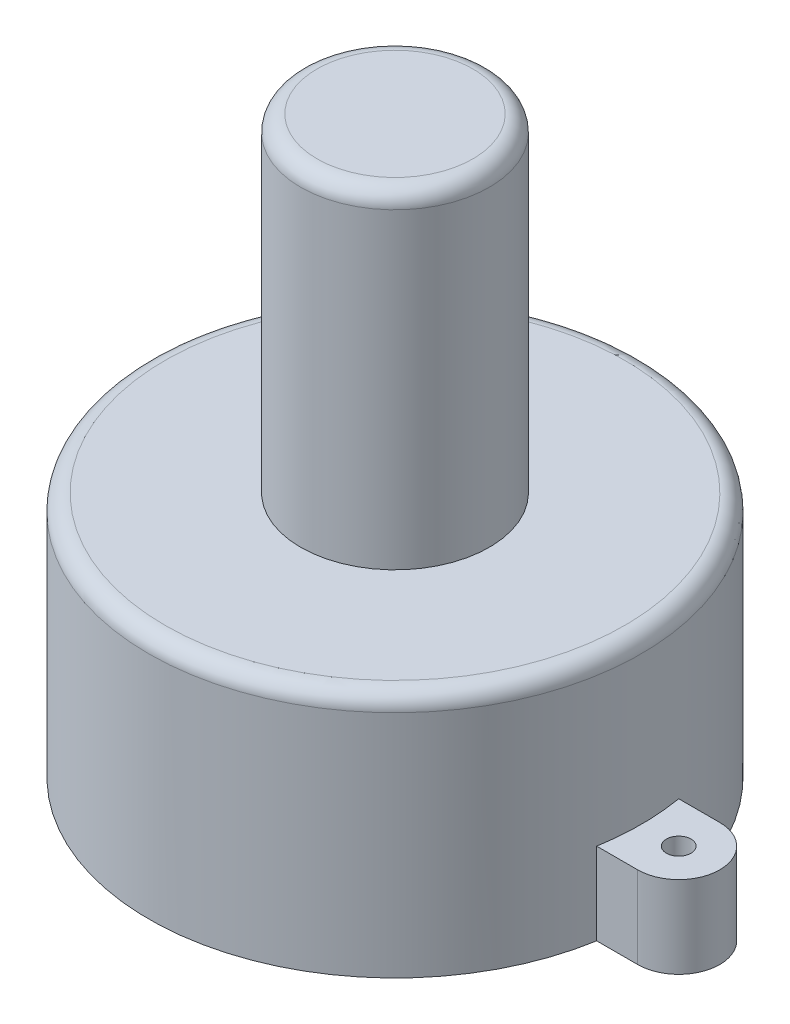
SolidWorks part; units mm, degrees
ref_plane "前基準面" through (0, 0, 0) normal (0, 0, 1) x (1, 0, 0)
ref_plane "上基準面" through (0, 0, 0) normal (0, 1, 0) x (1, 0, 0)
ref_plane "右基準面" through (0, 0, 0) normal (1, 0, 0) x (0, 0, -1)
sketch "草圖1" plane through (0, 0, 0) normal (0, 1, 0) x (1, 0, 0)
  circle A0 centre (0, 0) radius 30
  circle A1 centre (0, 0) radius 11.5
  dimension "D1" = 23
  dimension "D2" = 60
extrude "填料-伸長1" add sketch "草圖1" along normal blind 30 contours A0 A1 | A1 region at (-29.1515, 0, 0) region at (0, 0, 0)
extrude "填料-伸長2" add sketch "草圖1<3>" along normal blind 70 contours A1 region at (0, 0, 0)
sketch "草圖1<3>" plane through (0, 0, 0) normal (0, 1, 0) x (1, 0, 0) same geometry as "草圖1"
sketch "草圖3" plane through (0, 0, 0) normal (0, -1, 0) x (1, 0, 0)
  line L0 (0, 0) -> (0, 42.7) construction
  line L1 (0, 0) -> (52.9231, 0) construction
  line L2 (29.5804, 5) -> (39.5804, 5)
  line L3 (39.5804, 5) -> (39.5804, -5)
  line L4 (29.5804, -5) -> (39.5804, -5)
  line L5 (-29.5804, -5) -> (-39.5804, -5)
  line L6 (-39.5804, 5) -> (-39.5804, -5)
  line L7 (-29.5804, 5) -> (-39.5804, 5)
  circle A0 centre (0, 0) radius 30 construction
  arc A1 (29.5804, -5) -> (29.5804, 5) centre (0, 0) ccw
  arc A2 (-29.5804, -5) -> (-29.5804, 5) centre (0, 0) cw
  point P7 (39.5804, 0)
  dimension "D1" = 10
  dimension "D2" = 5
extrude "填料-伸長3" add sketch "草圖3" against normal blind 10
fillet "圓角1" 2 edges at (-39.5804, 5, 5) (-39.5804, 5, -5) type full round first side face at (-34.5804, 5, 5) second side face at (-34.5804, 5, -5) middle face at (-39.5804, 5, 0)
fillet "圓角2" 2 edges at (39.5804, 5, 5) (39.5804, 5, -5) type full round first side face at (34.5804, 5, 5) second side face at (34.5804, 5, -5) middle face at (39.5804, 5, 0)
sketch "草圖4" plane through (0, 10, 0) normal (0, 1, 0) x (1, 0, 0)
  circle A0 centre (34.5804, 0) radius 1.5
  circle A1 centre (-34.5804, 0) radius 1.5
  dimension "D1" = 3
  dimension "D2" = 3
extrude "除料-伸長1" cut sketch "草圖4" against normal through all
fillet "圓角3" radius 2 2 edges at (0, 70, 11.5) (0, 30, 30)
